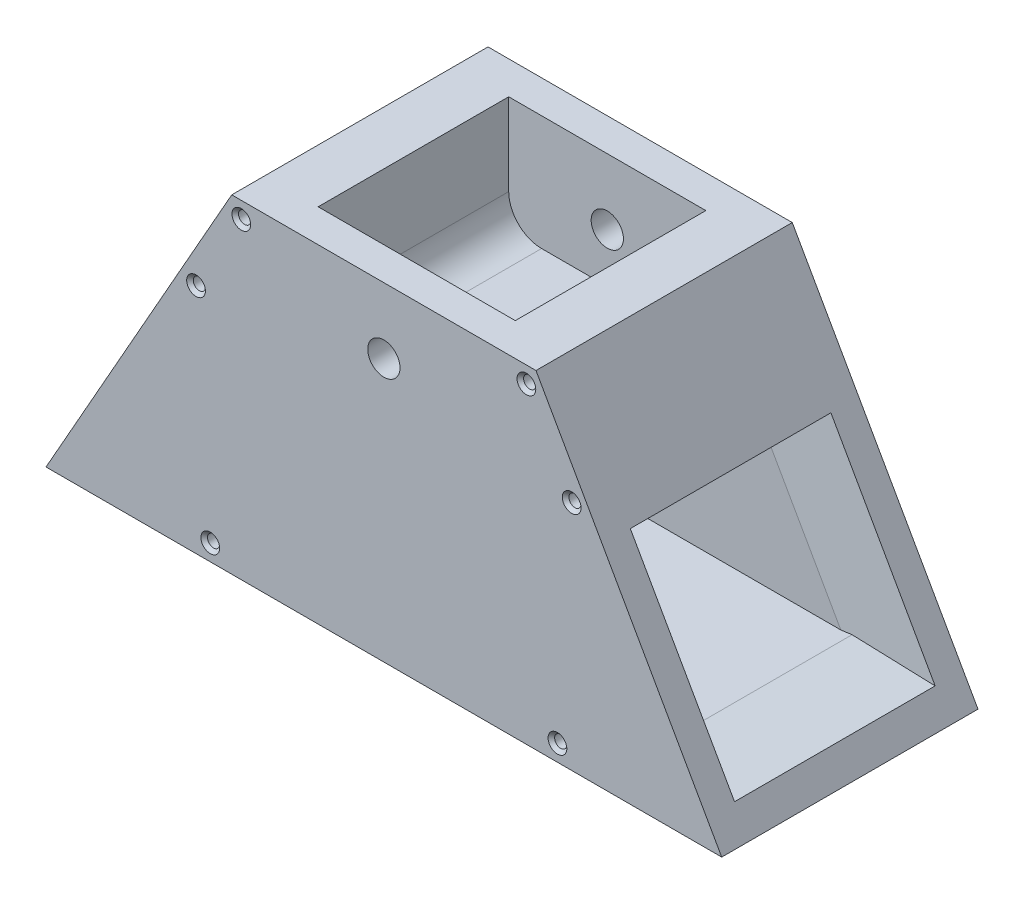
SolidWorks part; units mm, degrees
ref_plane "Front Plane" through (0, 0, 0) normal (0, 0, 1) x (1, 0, 0)
ref_plane "Top Plane" through (0, 0, 0) normal (0, 1, 0) x (1, 0, 0)
ref_plane "Right Plane" through (0, 0, 0) normal (1, 0, 0) x (0, 0, -1)
sketch "Sketch2" plane through (0, 0, 0) normal (0, 0, 1) x (1, 0, 0)
  line L0 (46.3, 100) -> (-46.3, 100)
  line L1 (-46.3, 100) -> (-102.8312, 0)
  line L2 (-102.8312, 0) -> (102.8312, 0)
  line L3 (0, 0) -> (0, 100) construction
  line L4 (46.3, 100) -> (102.8312, 0)
  dimension "D1" = 100
  dimension "D2" = 92.6
  dimension "D3" = 119.48
extrude "Boss-Extrude1" add sketch "Sketch2" along normal blind 78
sketch "Sketch3" plane through (0, 0, 0) normal (1, 0, 0) x (0, 0, -1)
  line L0 (-39, 0) -> (-39, 100) construction
  line L1 (-64.5, 13.5) -> (-13.5, 13.5) construction
  line L2 (-64.5, 13.5) -> (-64.5, 59.5) construction
  line L3 (-64.5, 59.5) -> (-13.5, 59.5) construction
  line L4 (-13.5, 13.5) -> (-13.5, 59.5) construction
  line L5 (-78, 0) -> (0, 0) construction
  line L6 (-78, 100) -> (0, 100) construction
  line L7 (-12, 32.8198) -> (0, 32.8198) construction
  line L8 (-66, 12) -> (-12, 12)
  line L9 (-12, 12) -> (-12, 61)
  line L10 (-66, 61) -> (-12, 61)
  line L11 (-66, 12) -> (-66, 61)
  line L12 (0, 0) -> (0, 100) construction
  line L13 (-20.3149, 12) -> (-20.3149, 0) construction
  dimension "D1" = 51
  dimension "D2" = 46
  dimension "D3" = 1.5
extrude "Cut-Extrude1" cut sketch "Sketch3" against normal through all and the other way through all
chamfer "Chamfer1" distance 20 angle 10 8 edges at (-82.1973, 36.5, 12) (-96.0475, 12, 39) (-82.1973, 36.5, 66) (-68.3472, 61, 39) (96.0475, 12, 39) (82.1973, 36.5, 12) (68.3472, 61, 39) (82.1973, 36.5, 66) first distance on face at (0, 36.5, 12) first distance on face at (0, 12, 39) first distance on face at (0, 36.5, 66) first distance on face at (0, 61, 39)
sketch "Sketch4" plane through (0, 0, 78) normal (0, 0, 1) x (1, 0, 0)
  line L0 (46.3, 100) -> (-46.3, 100) construction
  line L1 (-20, 65) -> (20, 65)
  line L2 (-30, 75) -> (-30, 100)
  line L3 (-30, 100) -> (30, 100)
  line L4 (30, 75) -> (30, 100)
  line L5 (-30, 65) -> (30, 100) construction
  line L6 (-30, 100) -> (30, 65) construction
  arc A0 (20, 65) -> (30, 75) centre (20, 75) ccw
  arc A1 (-20, 65) -> (-30, 75) centre (-20, 75) cw
  point P0 (0, 82.5)
  point P13 (0, 100)
  dimension "D1" = 10
  dimension "D2" = 35
  dimension "D3" = 60
extrude "Cut-Extrude2" cut sketch "Sketch4" against normal through all
sketch "Sketch8" plane through (0, 0, 78) normal (0, 0, 1) x (1, 0, 0)
  line L0 (-30, 100) -> (-46.3, 100) construction
  line L1 (0, 0) -> (0, 80) construction
  line L2 (30, 75) -> (30, 100) construction
  line L3 (-30, 100) -> (30, 100)
  line L4 (-30, 100) -> (-30, 53.856)
  line L5 (-30, 53.856) -> (30, 53.856)
  line L6 (30, 100) -> (30, 53.856)
  circle A0 centre (0, 80) radius 4.91
  dimension "D1" = 9.82
  dimension "D2" = 20
extrude "Boss-Extrude4" add sketch "Sketch8" against normal blind 10 contours L4 L3 L6 L5 | A0
extrude "Boss-Extrude5" add sketch "Sketch8<3>" along normal blind 10 from surface starting at face at (0, 67.5858, 0)
sketch "Sketch8<3>" plane through (0, 0, 78) normal (0, 0, 1) x (1, 0, 0) same geometry as "Sketch8"
sketch "Sketch10" plane through (0, 0, 78) normal (0, 0, 1) x (1, 0, 0)
  line L0 (-43.3829, 95) -> (-57.1623, 70.6252) construction
  line L1 (-46.3, 100) -> (-102.8312, 0) construction
  line L2 (0, 100) -> (0, 0) construction
  line L3 (46.3, 100) -> (-46.3, 100) construction
  line L4 (-102.8312, 0) -> (102.8312, 0) construction
  circle A0 centre (-43.3829, 95) radius 1.85
  circle A1 centre (-57.1623, 70.6252) radius 1.85
  circle A2 centre (-52.8312, 5) radius 1.85
  circle A3 centre (52.8312, 5) radius 1.85
  circle A4 centre (57.1623, 70.6252) radius 1.85
  circle A5 centre (43.3829, 95) radius 1.85
  dimension "D1" = 3.7
  dimension "D2" = 5
  dimension "D3" = 5
  dimension "D4" = 28
  dimension "D5" = 5
  dimension "D6" = 50
extrude "Cut-Extrude4" cut sketch "Sketch10" against normal through all
chamfer "Chamfer2" distance 1 angle 45 12 edges at (-55.3123, 70.6252, 0) (-50.9812, 5, 0) (50.9812, 5, 0) (55.3123, 70.6252, 0) (41.5329, 95, 0) (-41.5329, 95, 0) (-55.3123, 70.6252, 78) (-50.9812, 5, 78) (50.9812, 5, 78) (55.3123, 70.6252, 78) (41.5329, 95, 78) (-41.5329, 95, 78)
equation "\"D3@Sketch10\"=\"D2@Sketch10\""
equation "\"D5@Sketch10\"=\"D2@Sketch10\""
